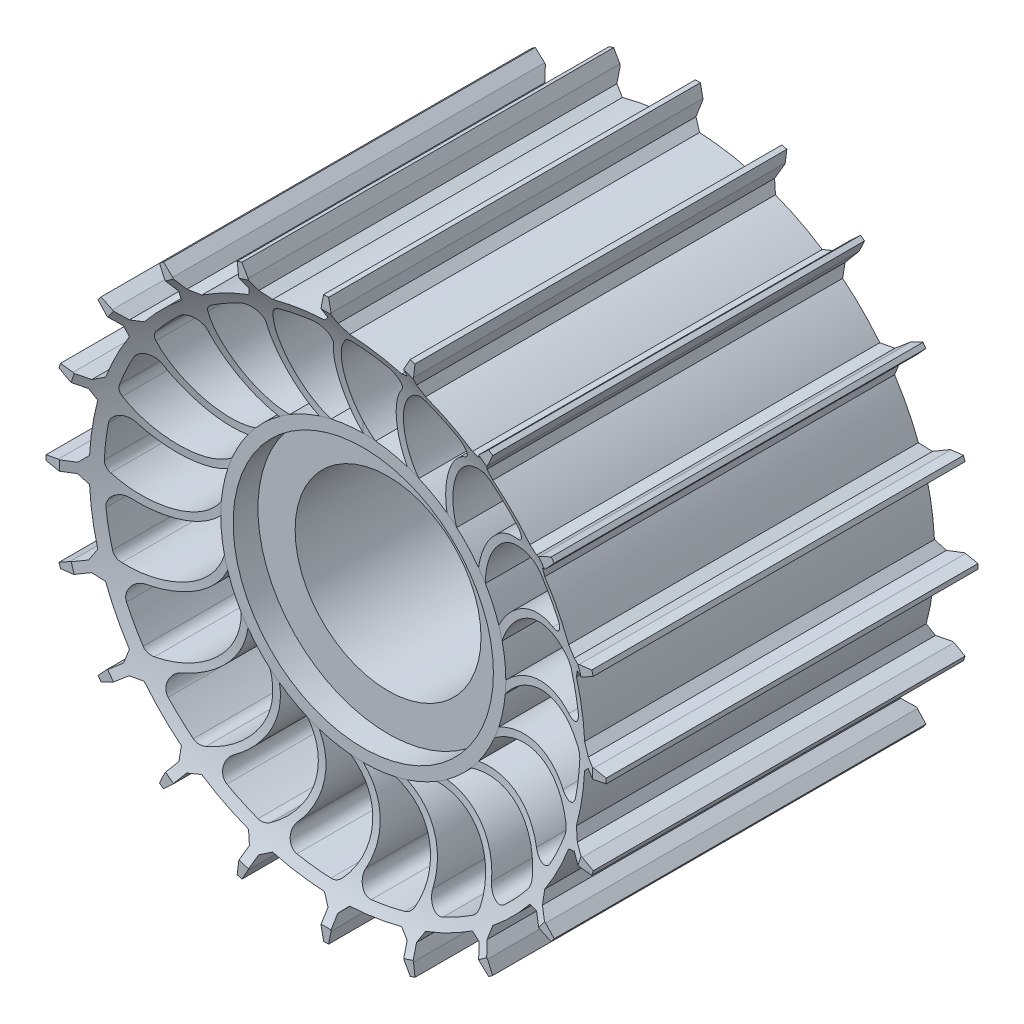
SolidWorks part; units mm, degrees
note: The reader was unsure of these and kept them because the rebuilt part matched: shared geometry of "Sketch2<3>".
ref_plane "Front Plane" through (0, 0, 0) normal (0, 0, 1) x (1, 0, 0)
ref_plane "Top Plane" through (0, 0, 0) normal (0, 1, 0) x (1, 0, 0)
ref_plane "Right Plane" through (0, 0, 0) normal (1, 0, 0) x (0, 0, -1)
sketch "Sketch1" plane through (0, 0, 0) normal (0, 0, 1) x (1, 0, 0)
  circle A0 centre (0, 0) radius 96
  circle A1 centre (0, 0) radius 100
  dimension "D1" = 4
  dimension "D2" = 200
extrude "Boss-Extrude1" add sketch "Sketch1" along normal mid plane 150
sketch "Sketch2" plane through (0, 0, 0) normal (0, 0, 1) x (1, 0, 0)
  line L0 (0, 0) -> (0, 98) construction
  line L1 (-2, 113) -> (2, 113)
  line L2 (-2, 113) -> (-2, 98)
  line L3 (-2, 98) -> (2, 98)
  line L4 (2, 113) -> (2, 98)
  line L5 (0, 98) -> (4.6767, 98)
  circle A1 centre (0, 0) radius 57.5 construction
  arc A2 (0, 98) -> (0, 57.5) centre (19.3375, 77.75) ccw
  arc A3 (4.9799, 57.284) -> (4.6767, 98) centre (19.3375, 77.75) cw
  arc A4 (4.9799, 57.284) -> (0, 57.5) centre (0, 0) ccw
  point P14 (5.672, 119)
  dimension "D4" = 115
  dimension "D5" = 3
  dimension "D6" = 25
  dimension "D1" = 15
  dimension "D2" = 4
  dimension "D3" = 98
extrude "Boss-Extrude2" add sketch "Sketch2" along normal mid plane 150 contours L4 L3 L2 L1
chamfer "Chamfer1" distance 3 angle 45 2 edges at (2, 99.98, 0) (-2, 99.98, 0)
chamfer "Chamfer2" distance 5 distance2 1 2 edges at (-2, 113, 0) (2, 113, 0)
pattern_circular "CirPattern1" count 20 over 360 about axis through (0, 0, 0) along (0, 0, 1) of "Boss-Extrude2", "Chamfer1", "Chamfer2"
extrude "Boss-Extrude3" add sketch "Sketch2<3>" along normal mid plane 150 contours A4 A3 L5 L3 A2
sketch "Sketch2<3>" plane through (0, 0, 0) normal (0, 0, 1) x (1, 0, 0) same geometry as "Sketch2"
fillet "Fillet1" radius 5 2 edges at (2.2238, 95.9742, 0) (-1.9142, 95.9809, 0)
pattern_circular "CirPattern3" count 20 over 360 about axis through (0, 0, 0) along (0, 0, 1) of "Boss-Extrude3", "Fillet1"
sketch "Sketch3" plane through (0, 0, 0) normal (1, 0, 0) x (0, 0, -1)
  line L0 (0, 0) -> (-75, 0) construction
  line L1 (-75, 0) -> (-75, 107.5) construction
  line L2 (-75, 57.5) -> (-60, 57.5)
  line L5 (-75, 107.5) -> (-75, 57.5)
  line L6 (-60, 57.5) -> (-60, 107.5) construction
  line L7 (0, 0) -> (0, 113) construction
  line L8 (-75, 113) -> (75, 113) construction
  line L9 (75, 57.5) -> (60, 57.5)
  line L10 (75, 107.5) -> (75, 57.5)
  arc A1 (-60, 57.5) -> (-75, 107.5) centre (-150.8333, 57.5) ccw
  arc A2 (60, 57.5) -> (75, 107.5) centre (150.8333, 57.5) cw
  dimension "D1" = 57.5
  dimension "D2" = 15
  dimension "D3" = 50
revolve "Cut-Revolve1" cut sketch "Sketch3" angle 360 about L0
sketch "Sketch4" plane through (0, 0, 0) normal (0, 0, 1) x (1, 0, 0)
  circle A0 centre (0, 0) radius 57.5
  circle A2 centre (0, 0) radius 37.5
  dimension "D1" = 20
extrude "Boss-Extrude4" add sketch "Sketch4" along normal mid plane 120
sketch "Sketch5" plane through (0, 0, 60) normal (0, 0, 1) x (1, 0, 0)
  circle A0 centre (0, 0) radius 52.5
  arc A1 (0, 57.5) -> (-12.9656, 56.0191) centre (0, 0) ccw construction
  dimension "D1" = 5
extrude "Cut-Extrude1" cut sketch "Sketch5" against normal blind 10
mirror "Mirror1" about plane through (0, 0, 0) normal (0, 0, 1) of "Cut-Extrude1"
